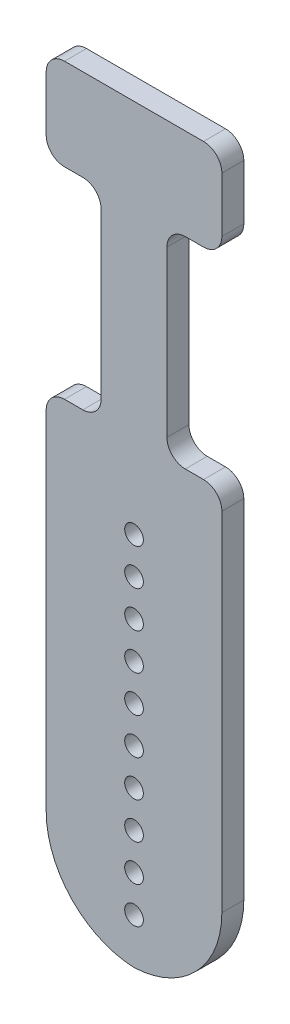
SolidWorks part; units mm, degrees
other "Markup1"
sketch "Sketch7" plane through (-20, 225, -2) normal (-0.1146, 0.1086, -0.9875) x (-0.991, 0.0573, 0.1213)
sketch "Sketch10" plane through (-20, 225, -2) normal (-0.1146, 0.1086, -0.9875) x (-0.991, 0.0573, 0.1213)
sketch "Sketch11" plane through (-20, 225, -2) normal (-0.1146, 0.1086, -0.9875) x (-0.991, 0.0573, 0.1213)
sketch "Sketch13" plane through (-25, 225, -3) normal (-0.1146, 0.1086, -0.9875) x (-0.991, 0.0573, 0.1213)
sketch "Sketch14" plane through (-24, 225, -3) normal (-0.1146, 0.1086, -0.9875) x (-0.991, 0.0573, 0.1213)
sketch "Sketch15" plane through (-24, 225, -3) normal (-0.1146, 0.1086, -0.9875) x (-0.991, 0.0573, 0.1213)
sketch "Sketch20" plane through (-24, 225, -3) normal (-0.1146, 0.1086, -0.9875) x (-0.991, 0.0573, 0.1213)
sketch "Sketch21" plane through (-24, 225, -3) normal (-0.1146, 0.1086, -0.9875) x (-0.991, 0.0573, 0.1213)
ref_plane "Front Plane" through (0, 0, 0) normal (0, 0, 1) x (1, 0, 0)
ref_plane "Top Plane" through (0, 0, 0) normal (0, 1, 0) x (1, 0, 0)
ref_plane "Right Plane" through (0, 0, 0) normal (1, 0, 0) x (0, 0, -1)
sketch "Sketch1" plane through (0, 0, 0) normal (0, 1, 0) x (1, 0, 0)
  line L1 (-24, 3) -> (24, 3)
  line L2 (-24, 3) -> (-24, -3)
  line L3 (-24, -3) -> (24, -3)
  line L4 (24, 3) -> (24, -3)
  line L5 (-24, 3) -> (24, -3) construction
  line L6 (-24, -3) -> (24, 3) construction
  point P0 (0, 0)
  dimension "D1" = 6
  dimension "D2" = 48
extrude "Boss-Extrude1" add sketch "Sketch1" along normal blind 205
fillet "Fillet1" radius 25 2 edges at (-24, 0, 0) (24, 0, 0)
sketch "Sketch2" plane through (0, 0, 3) normal (0, 0, 1) x (1, 0, 0)
  circle A0 centre (0, 12.5) radius 2.55
extrude "Cut-Extrude1" cut sketch "Sketch2" against normal through all
pattern_linear "LPattern1" count 10 spacing 10 along (0, 1, 0) of "Cut-Extrude1"
sketch "Sketch12" plane through (0, 0, 0) normal (0, 0, 1) x (1, 0, 0)
  line L3 (-24, 180) -> (24, 180)
  line L5 (0, 232.0388) -> (0, 196.5997) construction
  line L6 (-9, 180) -> (-9, 125)
  line L7 (9, 180) -> (9, 125)
  line L8 (9, 125) -> (24, 125)
  line L9 (24, 205) -> (24, 25) construction
  line L10 (24, 125) -> (24, 180)
  line L12 (-9, 125) -> (-24, 125)
  line L13 (-24, 205) -> (-24, 25) construction
  line L14 (-24, 125) -> (-24, 180)
  line L15 (24, 205) -> (-24, 205) construction
  dimension "D1" = 15
  dimension "D2" = 55
  dimension "D3" = 18
  dimension "D4" = 9
  dimension "D5" = 55
  dimension "D6" = 48
  dimension "D7" = 55
  dimension "D8" = 15
  dimension "D9" = 25
extrude "Cut-Extrude2" cut sketch "Sketch12" against normal through all both and the other way through all contours L12 L6 L3 | L3 L7 L8 region at (16.5, 152.5, 0) region at (-16.5, 152.5, 0)
fillet "Fillet2" radius 5 10 edges at (-24, 125, 0) (-9, 125, 0) (24, 125, 0) (9, 125, 0) (9, 180, 0) (-9, 180, 0) (-24, 205, 0) (-24, 180, 0) (24, 180, 0) (24, 205, 0)
